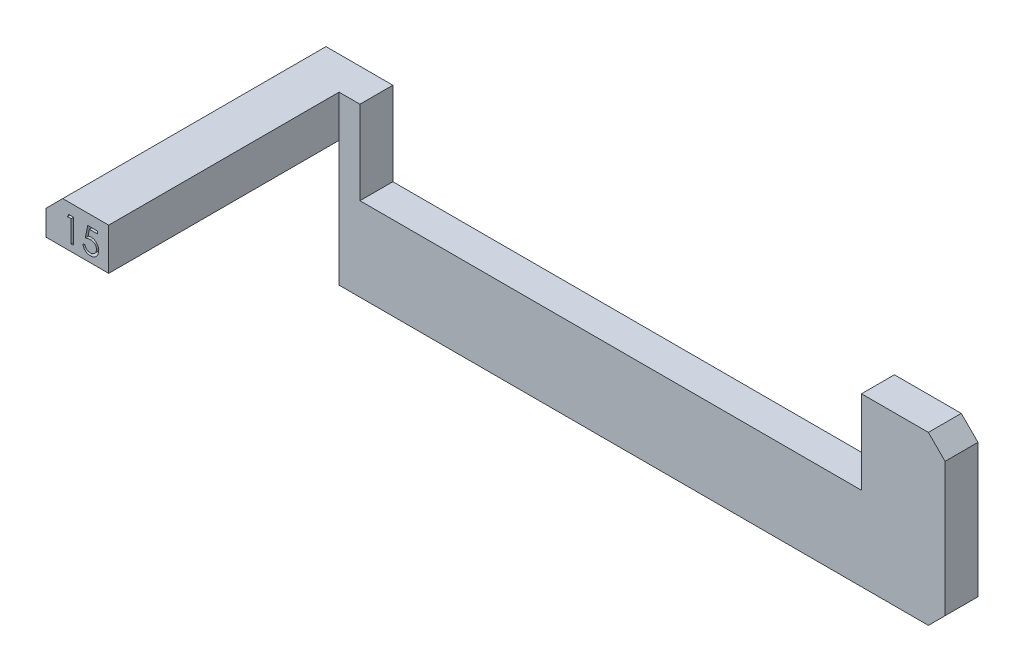
SolidWorks part; units mm, degrees
ref_plane "Front Plane" through (0, 0, 0) normal (0, 0, 1) x (1, 0, 0)
ref_plane "Top Plane" through (0, 0, 0) normal (0, 1, 0) x (1, 0, 0)
ref_plane "Right Plane" through (0, 0, 0) normal (1, 0, 0) x (0, 0, -1)
sketch "Sketch1" plane through (0, 0, 0) normal (0, 0, 1) x (1, 0, 0)
  line L1 (0, 0) -> (-101.6, 0)
  line L2 (0, 0) -> (0, 25.4)
  line L3 (0, 25.4) -> (-101.6, 25.4)
  line L4 (-101.6, 0) -> (-101.6, 25.4)
  line L5 (-12.7, 25.4) -> (-88.9, 25.4)
  line L6 (-12.7, 25.4) -> (-12.7, 12.7)
  line L7 (-12.7, 12.7) -> (-88.9, 12.7)
  line L8 (-88.9, 25.4) -> (-88.9, 12.7)
  point P9 (-50.8, 25.4)
  point P10 (-50.8, 12.7)
  dimension "D1" = 101.6
  dimension "D2" = 25.4
  dimension "D3" = 12.7
  dimension "D4" = 12.7
extrude "Boss-Extrude1" add sketch "Sketch1" along normal blind 5 contours L8 L3 L4 L1 L2 L6 L7 region at (-50.8, 8.89, 0)
sketch "Sketch2" plane through (0, 0, 5) normal (0, 0, 1) x (1, 0, 0)
  line L0 (0, 0) -> (-101.6, 0) construction
  line L1 (-101.6, 19.05) -> (-92.075, 19.05)
  line L2 (-101.6, 19.05) -> (-101.6, 25.4)
  line L3 (-101.6, 25.4) -> (-92.075, 25.4)
  line L4 (-92.075, 19.05) -> (-92.075, 25.4)
  line L5 (-101.6, 0) -> (-101.6, 25.4) construction
  dimension "D1" = 9.525
  dimension "D2" = 6.35
  dimension "D3" = 19.05
extrude "Boss-Extrude2" add sketch "Sketch2" along normal blind 35
sketch "Sketch3" plane through (0, 0, 40) normal (0, 0, 1) x (1, 0, 0)
  line L0 (-101.6, 25.4) -> (-101.6, 19.05) construction
  line L2 (-101.6, 19.05) -> (-92.075, 19.05) construction
  text T0 "15" font "Century Gothic" height in points 14
  dimension "D1" = 2.54
  dimension "D2" = 1.016
extrude "Cut-Extrude1" cut sketch "Sketch3" against normal blind 2
chamfer "Chamfer1" distance 2.54 angle 45 4 edges at (0, 0, 2.5) (-101.6, 0, 2.5) (0, 25.4, 2.5) (-101.6, 25.4, 20)
sketch "Sketch4" plane through (0, 0, 5) normal (0, 0, 1) x (1, 0, 0)
  line L0 (-101.6, 2.54) -> (-101.6, 19.05) construction
  line L1 (-92.075, 19.05) -> (-101.6, 19.05)
  line L2 (-92.075, 19.05) -> (-92.075, 0)
  line L3 (-92.075, 0) -> (-101.6, 0)
  line L4 (-101.6, 19.05) -> (-101.6, 0)
  line L5 (-2.54, 0) -> (-99.06, 0) construction
extrude "Cut-Extrude2" cut sketch "Sketch4" against normal through all
